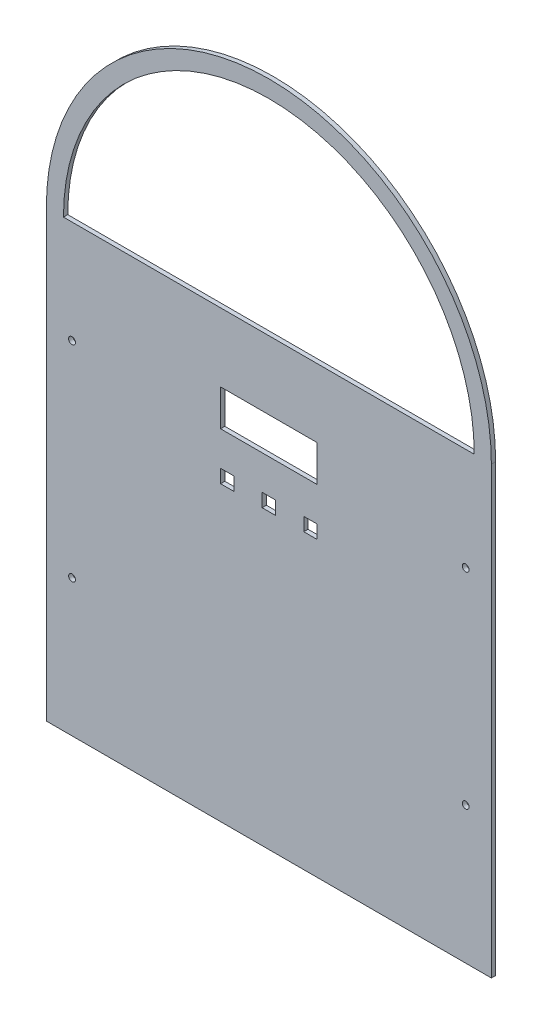
SolidWorks part; units mm, degrees
ref_plane "Front" through (0, 0, 0) normal (0, 0, 1) x (1, 0, 0)
ref_plane "Top" through (0, 0, 0) normal (0, 1, 0) x (1, 0, 0)
ref_plane "Right" through (0, 0, 0) normal (1, 0, 0) x (0, 0, -1)
sketch "Sketch1" plane through (0, 0, 0) normal (0, 0, 1) x (1, 0, 0)
  line L1 (12.7, 0) -> (317.5, 0)
  line L2 (0, 0) -> (0, -330.2)
  line L3 (0, -330.2) -> (330.2, -330.2)
  line L4 (330.2, 0) -> (330.2, -330.2)
  line L5 (129.286, -50.8) -> (200.914, -50.8)
  line L6 (129.286, -50.8) -> (129.286, -77.724)
  line L7 (129.286, -77.724) -> (200.914, -77.724)
  line L8 (200.914, -50.8) -> (200.914, -77.724)
  line L9 (129.286, -103.124) -> (139.192, -103.124)
  line L10 (129.286, -103.124) -> (129.286, -113.03)
  line L11 (129.286, -113.03) -> (139.192, -113.03)
  line L12 (139.192, -103.124) -> (139.192, -113.03)
  line L13 (160.147, -103.124) -> (170.053, -103.124)
  line L14 (160.147, -103.124) -> (160.147, -113.03)
  line L15 (160.147, -113.03) -> (170.053, -113.03)
  line L16 (170.053, -103.124) -> (170.053, -113.03)
  line L17 (191.008, -103.124) -> (200.914, -103.124)
  line L18 (191.008, -103.124) -> (191.008, -113.03)
  line L19 (191.008, -113.03) -> (200.914, -113.03)
  line L20 (200.914, -103.124) -> (200.914, -113.03)
  arc A0 (0, 0) -> (330.2, 0) centre (165.1, 0) cw
  arc A1 (12.7, 0) -> (317.5, 0) centre (165.1, 0) cw
  circle A2 centre (19.05, -76.2) radius 2.54
  circle A3 centre (19.05, -228.6) radius 2.54
  circle A4 centre (311.15, -76.2) radius 2.54
  circle A5 centre (311.15, -228.6) radius 2.54
  point P25 (165.1, -77.724)
  point P26 (165.1, -330.2)
  point P27 (165.1, -103.124)
  dimension "D3" = 12.7
  dimension "D15" = 5.08
  dimension "D17" = 5.08
  dimension "D20" = 5.08
  dimension "D21" = 5.08
  dimension "D1" = 330.2
  dimension "D2" = 330.2
  dimension "D4" = 71.628
  dimension "D5" = 26.924
  dimension "D6" = 9.906
  dimension "D7" = 9.906
  dimension "D8" = 9.906
  dimension "D9" = 9.906
  dimension "D10" = 9.906
  dimension "D11" = 9.906
  dimension "D12" = 25.4
  dimension "D13" = 50.8
  dimension "D14" = 19.05
  dimension "D16" = 19.05
  dimension "D18" = 19.05
  dimension "D19" = 19.05
  dimension "D22" = 152.4
  dimension "D23" = 101.6
  dimension "D24" = 152.4
  dimension "D25" = 101.6
extrude "Boss-Extrude1" add sketch "Sketch1" along normal blind 3.175
